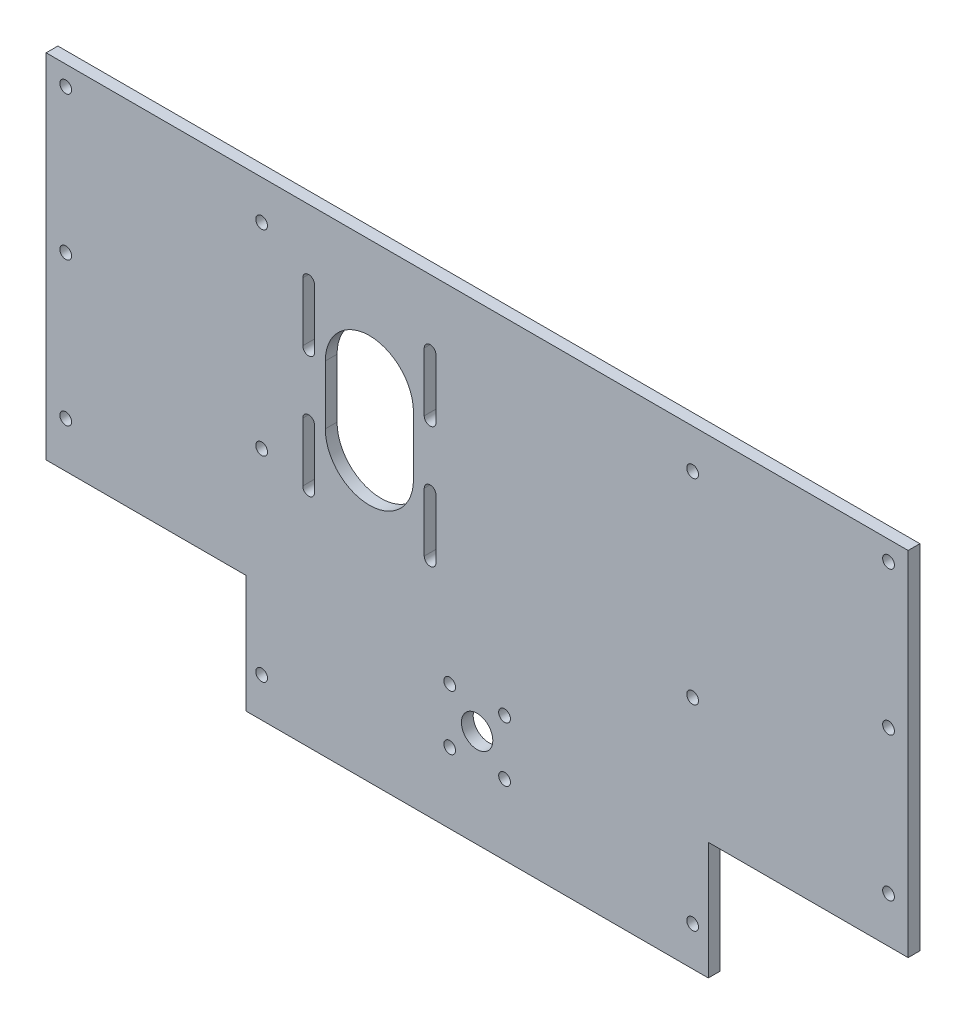
SolidWorks part; units mm, degrees
ref_plane "Plan de face" through (0, 0, 0) normal (0, 0, 1) x (1, 0, 0)
ref_plane "Plan de dessus" through (0, 0, 0) normal (0, 1, 0) x (1, 0, 0)
ref_plane "Plan de droite" through (0, 0, 0) normal (1, 0, 0) x (0, 0, -1)
sketch "Esquisse1" plane through (0, 0, 0) normal (0, 0, 1) x (1, 0, 0)
  line L0 (-27.5, 17.5) -> (-27.5, 32.5) construction
  line L1 (60, -65) -> (-60, -65) construction
  line L3 (60, 65) -> (-60, 65)
  line L4 (-60, -65) -> (-60, -34) construction
  line L5 (60, -65) -> (-60, 65) construction
  line L6 (60, 65) -> (-60, -65) construction
  line L9 (60, -55) -> (50, -55)
  line L10 (50, -65) -> (50, -55) construction
  line L13 (-60, -55) -> (-50, -55)
  line L15 (-38.75, 17.5) -> (-38.75, 32.5)
  line L16 (-16.25, 17.5) -> (-16.25, 32.5)
  line L17 (-43, 33) -> (-43, 48) construction
  line L18 (-44.5, 33) -> (-44.5, 48)
  line L19 (-41.5, 33) -> (-41.5, 48)
  line L20 (-43, 2) -> (-43, 17) construction
  line L21 (-44.5, 2) -> (-44.5, 17)
  line L22 (-41.5, 2) -> (-41.5, 17)
  line L23 (-27.5, 65) -> (-27.5, -65) construction
  line L24 (-27.5, 43.75) -> (-27.5, 6.25) construction
  line L27 (-12, 2) -> (-12, 17) construction
  line L30 (-10.5, 2) -> (-10.5, 17)
  line L31 (-13.5, 2) -> (-13.5, 17)
  line L32 (-12, 33) -> (-12, 48) construction
  line L33 (-10.5, 33) -> (-10.5, 48)
  line L34 (-13.5, 33) -> (-13.5, 48)
  line L35 (-105, -55) -> (-105, 65) construction
  line L36 (-60, -55) -> (-110, -55) construction
  line L38 (-60, 65) -> (-110, 65)
  line L42 (-60, -25) -> (-110, -25)
  line L44 (0, 65) -> (0, -65) construction
  line L45 (60, -25) -> (110, -25)
  line L49 (60, 65) -> (110, 65)
  line L50 (-55, -65) -> (-55, 65) construction
  line L51 (60, -55) -> (110, -55) construction
  line L52 (-50, -55) -> (50, -55)
  line L53 (-110, -25) -> (-110, 65)
  line L54 (60, -25) -> (60, -55) construction
  line L55 (-60, -25) -> (-50, -25) construction
  line L58 (-50, -25) -> (-50, -65) construction
  line L59 (50, -25) -> (50, -65) construction
  line L60 (60, -25) -> (50, -25) construction
  line L61 (110, -25) -> (110, 65)
  line L62 (-60, -25) -> (-60, 65) construction
  line L64 (60, -25) -> (60, 65) construction
  line L65 (-60, -55) -> (-60, -25) construction
  line L66 (60, -25) -> (59, -25)
  line L67 (59, -25) -> (59, -55)
  line L68 (-60, -25) -> (-59, -25)
  line L69 (-59, -25) -> (-59, -55)
  arc A0 (-38.75, 17.5) -> (-16.25, 17.5) centre (-27.5, 17.5) ccw
  arc A1 (-16.25, 32.5) -> (-38.75, 32.5) centre (-27.5, 32.5) ccw
  arc A2 (-44.5, 33) -> (-41.5, 33) centre (-43, 33) ccw
  arc A3 (-41.5, 48) -> (-44.5, 48) centre (-43, 48) ccw
  arc A4 (-44.5, 2) -> (-41.5, 2) centre (-43, 2) ccw
  arc A5 (-41.5, 17) -> (-44.5, 17) centre (-43, 17) ccw
  arc A10 (-10.5, 2) -> (-13.5, 2) centre (-12, 2) cw
  arc A11 (-13.5, 17) -> (-10.5, 17) centre (-12, 17) cw
  arc A12 (-10.5, 33) -> (-13.5, 33) centre (-12, 33) cw
  arc A13 (-13.5, 48) -> (-10.5, 48) centre (-12, 48) cw
  circle A14 centre (-105, -50) radius 1.5
  circle A15 centre (-105, -13.3333) radius 1.5
  circle A16 centre (-105, 23.3333) radius 1.5
  circle A17 centre (-105, 60) radius 1.5
  circle A18 centre (105, -50) radius 1.5
  circle A19 centre (105, -13.3333) radius 1.5
  circle A20 centre (105, 23.3333) radius 1.5
  circle A21 centre (105, 60) radius 1.5
  circle A29 centre (-55, -45) radius 1.5
  circle A30 centre (-55, 5) radius 1.5
  circle A31 centre (-55, 55) radius 1.5
  circle A32 centre (55, 55) radius 1.5
  circle A33 centre (55, 5) radius 1.5
  circle A34 centre (55, -45) radius 1.5
  point P0 (0, 0)
  point P14 (-27.5, 25)
  point P21 (-43, 40.5)
  point P28 (-43, 9.5)
  point P37 (-12, 9.5)
  point P44 (-12, 40.5)
  dimension "D13" = 90
  dimension "D17" = 3
  dimension "D22" = 3
  dimension "D23" = 10
  dimension "D15" = 3
  dimension "D1" = 10
  dimension "D2" = 10
  dimension "D3" = 130
  dimension "D4" = 120
  dimension "D5" = 32.5
  dimension "D6" = 15.5
  dimension "D7" = 22.5
  dimension "D8" = 3
  dimension "D9" = 15.5
  dimension "D10" = 15
  dimension "D11" = 3
  dimension "D12" = 31
  dimension "D14" = 5
  dimension "D16" = 10
  dimension "D18" = 5
  dimension "D19" = 5
  dimension "D20" = 50
  dimension "D24" = 10
  dimension "D21" = 4
extrude "Boss.-Extru.1" add sketch "Esquisse1" along normal blind 3 contours L1 L10 L9 L3 L4 L13 A5 L22 A4 L21 A3 L19 A2 L18 A1 L16 A0 L15 L31 A11 L30 A10 L34 A13 L33 A12 | L42 L4 L38 A17 A16 A15 | L45 L49 A20 A19 A21 | L51 A18 | L4 L36 A14 region at (1.1627, 10.2911, 0)
sketch "Esquisse3" plane through (0, 0, 3) normal (0, 0, 1) x (1, 0, 0)
  line L0 (-59, -55) -> (59, -55) construction
  line L4 (0, 65) -> (0, -42) construction
  line L5 (110, 65) -> (-110, 65) construction
  line L6 (-7, -23) -> (7, -23) construction
  line L7 (7, -42) -> (-7, -42) construction
  line L8 (12, -37) -> (12, -23) construction
  line L9 (7, -18) -> (-7, -18) construction
  line L10 (-12, -37) -> (-12, -23) construction
  line L11 (12, -42) -> (-12, -18) construction
  line L12 (12, -18) -> (-12, -42) construction
  line L13 (-7, -23) -> (-7, -37) construction
  circle A0 centre (0, -30) radius 4
  arc A2 (-7, -42) -> (-12, -37) centre (-7, -37) cw construction
  arc A3 (7, -42) -> (12, -37) centre (7, -37) ccw construction
  arc A4 (12, -23) -> (7, -18) centre (7, -23) ccw construction
  arc A5 (-7, -18) -> (-12, -23) centre (-7, -23) ccw construction
  circle A6 centre (-7, -23) radius 1.5
  circle A7 centre (7, -23) radius 1.5
  circle A8 centre (7, -37) radius 1.5
  circle A9 centre (-7, -37) radius 1.5
  dimension "D1" = 8
  dimension "D2" = 25
  dimension "D3" = 14
  dimension "D4" = 5
  dimension "D5" = 3
  dimension "D8" = 14
  dimension "D6" = 2
  dimension "D7" = 2
extrude "Enlèv. mat.-Extru.3" cut sketch "Esquisse3" against normal blind 10
